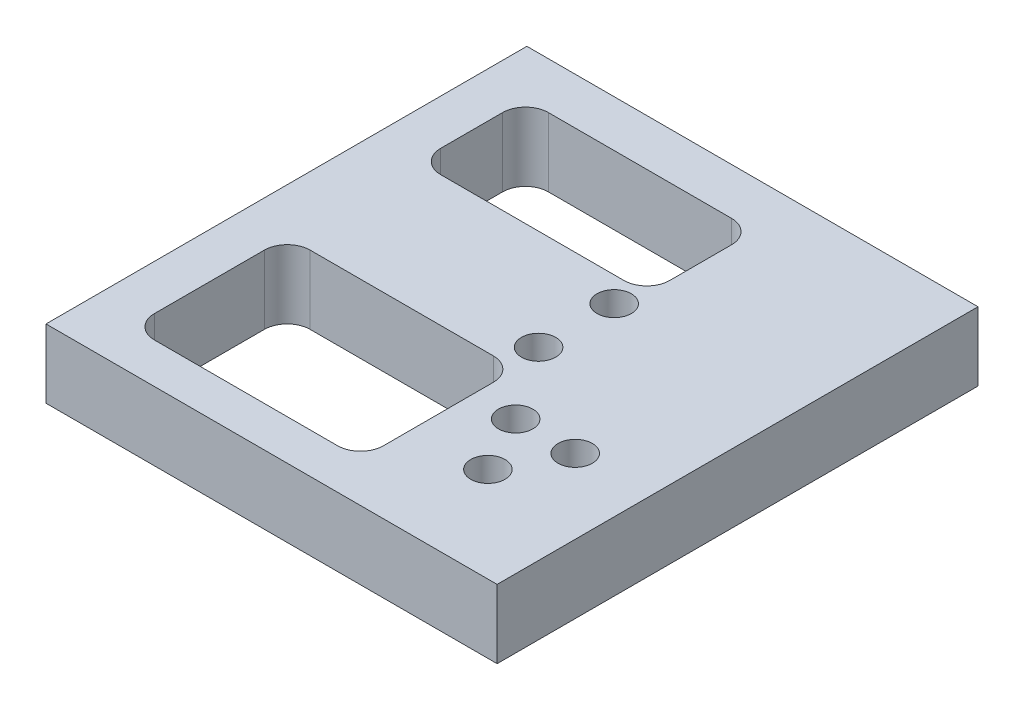
SolidWorks part; units mm, degrees
material "K110"
ref_plane "Front Plane" through (0, 0, 0) normal (0, 0, 1) x (1, 0, 0)
ref_plane "Top Plane" through (0, 0, 0) normal (0, 1, 0) x (1, 0, 0)
ref_plane "Right Plane" through (0, 0, 0) normal (1, 0, 0) x (0, 0, -1)
sketch "Sketch1" plane through (0, 0, 0) normal (0, 1, 0) x (1, 0, 0)
  line L1 (-98.5, -105) -> (98.5, -105)
  line L2 (-98.5, -105) -> (-98.5, 105)
  line L3 (-98.5, 105) -> (98.5, 105)
  line L4 (98.5, -105) -> (98.5, 105)
  line L5 (-98.5, -105) -> (98.5, 105) construction
  line L6 (-98.5, 105) -> (98.5, -105) construction
  point P0 (0, 0)
  dimension "D1" = 210
  dimension "D2" = 197
extrude "Boss-Extrude1" add sketch "Sketch1" against normal blind 30
sketch "Sketch2" plane through (0, 0, 0) normal (0, 1, 0) x (1, 0, 0)
  line L0 (-29.25, -63.53) -> (-29.25, -47.4) construction
  line L1 (-32.25, -44.4) -> (-36.25, -44.4) construction
  line L2 (-42.25, -38.4) -> (-42.25, -32.27) construction
  line L3 (-42.25, -32.27) -> (-61.37, -32.27) construction
  line L12 (-64.37, -35.27) -> (-64.37, -71.53) construction
  line L13 (-61.37, -74.53) -> (3.88, -74.53) construction
  line L14 (-17.25, -47.4) -> (-17.25, -63.53) construction
  line L15 (-10.25, -44.4) -> (-14.25, -44.4) construction
  line L16 (-4.25, -32.27) -> (-4.25, -38.4) construction
  line L17 (3.88, -32.27) -> (-4.25, -32.27) construction
  line L18 (6.88, -71.53) -> (6.88, -35.27) construction
  line L19 (-29.25, -63.53) -> (-29.25, -47.4)
  line L20 (-32.25, -44.4) -> (-36.25, -44.4)
  line L21 (-42.25, -38.4) -> (-42.25, -32.27)
  line L22 (-42.25, -32.27) -> (-61.37, -32.27)
  line L23 (-64.37, -35.27) -> (-64.37, -71.53)
  line L24 (-61.37, -74.53) -> (3.88, -74.53)
  line L25 (-17.25, -47.4) -> (-17.25, -63.53)
  line L26 (-10.25, -44.4) -> (-14.25, -44.4)
  line L27 (-4.25, -32.27) -> (-4.25, -38.4)
  line L28 (3.88, -32.27) -> (-4.25, -32.27)
  line L29 (6.88, -71.53) -> (6.88, -35.27)
  line L30 (-4.25, 47.73) -> (3.88, 47.73) construction
  line L31 (-4.25, 69.53) -> (-4.25, 47.73) construction
  line L32 (-42.25, 69.53) -> (-4.25, 69.53) construction
  line L33 (-42.25, 47.73) -> (-42.25, 69.53) construction
  line L34 (-61.37, 47.73) -> (-42.25, 47.73) construction
  line L35 (-64.37, 71.53) -> (-64.37, 50.73) construction
  line L36 (3.88, 74.53) -> (-61.37, 74.53) construction
  line L37 (6.88, 50.73) -> (6.88, 71.53) construction
  line L38 (-4.25, 47.73) -> (3.88, 47.73)
  line L39 (-4.25, 69.53) -> (-4.25, 47.73)
  line L40 (-42.25, 69.53) -> (-4.25, 69.53)
  line L41 (-42.25, 47.73) -> (-42.25, 69.53)
  line L42 (-61.37, 47.73) -> (-42.25, 47.73)
  line L43 (-64.37, 71.53) -> (-64.37, 50.73)
  line L44 (3.88, 74.53) -> (-61.37, 74.53)
  line L45 (6.88, 50.73) -> (6.88, 71.53)
  arc A0 (-29.25, -47.4) -> (-32.25, -44.4) centre (-32.25, -47.4) ccw construction
  arc A1 (-42.25, -38.4) -> (-36.25, -44.4) centre (-36.25, -38.4) ccw construction
  arc A2 (-61.37, -32.27) -> (-64.37, -35.27) centre (-61.37, -35.27) ccw construction
  arc A3 (-64.37, -71.53) -> (-61.37, -74.53) centre (-61.37, -71.53) ccw construction
  arc A4 (3.88, -74.53) -> (6.88, -71.53) centre (3.88, -71.53) ccw construction
  arc A5 (-29.25, -63.53) -> (-17.25, -63.53) centre (-23.25, -63.53) ccw construction
  arc A6 (-14.25, -44.4) -> (-17.25, -47.4) centre (-14.25, -47.4) ccw construction
  arc A7 (-10.25, -44.4) -> (-4.25, -38.4) centre (-10.25, -38.4) ccw construction
  arc A8 (6.88, -35.27) -> (3.88, -32.27) centre (3.88, -35.27) ccw construction
  arc A9 (-29.25, -47.4) -> (-32.25, -44.4) centre (-32.25, -47.4) ccw
  arc A10 (-42.25, -38.4) -> (-36.25, -44.4) centre (-36.25, -38.4) ccw
  arc A11 (-61.37, -32.27) -> (-64.37, -35.27) centre (-61.37, -35.27) ccw
  arc A12 (-64.37, -71.53) -> (-61.37, -74.53) centre (-61.37, -71.53) ccw
  arc A13 (3.88, -74.53) -> (6.88, -71.53) centre (3.88, -71.53) ccw
  arc A14 (-29.25, -63.53) -> (-17.25, -63.53) centre (-23.25, -63.53) ccw
  arc A15 (-14.25, -44.4) -> (-17.25, -47.4) centre (-14.25, -47.4) ccw
  arc A16 (-10.25, -44.4) -> (-4.25, -38.4) centre (-10.25, -38.4) ccw
  arc A17 (6.88, -35.27) -> (3.88, -32.27) centre (3.88, -35.27) ccw
  circle A18 centre (53, -63.53) radius 2.5 construction
  circle A19 centre (66, -38.4) radius 2.5 construction
  circle A20 centre (40, -38.4) radius 2.5 construction
  circle A21 centre (17.88, -6.27) radius 2.5 construction
  circle A22 centre (17.88, 26.73) radius 2.5 construction
  arc A23 (3.88, 47.73) -> (6.88, 50.73) centre (3.88, 50.73) ccw construction
  arc A24 (-64.37, 50.73) -> (-61.37, 47.73) centre (-61.37, 50.73) ccw construction
  arc A25 (-61.37, 74.53) -> (-64.37, 71.53) centre (-61.37, 71.53) ccw construction
  arc A26 (6.88, 71.53) -> (3.88, 74.53) centre (3.88, 71.53) ccw construction
  circle A27 centre (53, -63.53) radius 2.5
  circle A28 centre (66, -38.4) radius 2.5
  circle A29 centre (40, -38.4) radius 2.5
  circle A30 centre (17.88, -6.27) radius 2.5
  circle A31 centre (17.88, 26.73) radius 2.5
  arc A32 (3.88, 47.73) -> (6.88, 50.73) centre (3.88, 50.73) ccw
  arc A33 (-64.37, 50.73) -> (-61.37, 47.73) centre (-61.37, 50.73) ccw
  arc A34 (-61.37, 74.53) -> (-64.37, 71.53) centre (-61.37, 71.53) ccw
  arc A35 (6.88, 71.53) -> (3.88, 74.53) centre (3.88, 71.53) ccw
sketch "Sketch3" plane through (0, 0, 0) normal (0, 1, 0) x (1, 0, 0)
  line L1 (-68.745, 84.63) -> (11.255, 84.63)
  line L2 (-78.745, 74.63) -> (-78.745, 47.63)
  line L3 (-68.745, 37.63) -> (11.255, 37.63)
  line L4 (21.255, 74.63) -> (21.255, 47.63)
  line L8 (-64.37, -53.4) -> (6.88, -53.4) construction
  line L9 (-68.745, -19.4) -> (11.255, -19.4)
  line L10 (-78.745, -29.4) -> (-78.745, -77.4)
  line L11 (-68.745, -87.4) -> (11.255, -87.4)
  line L12 (21.255, -29.4) -> (21.255, -77.4)
  line L13 (-64.37, -35.27) -> (-64.37, -71.53) construction
  line L14 (6.88, -71.53) -> (6.88, -35.27) construction
  line L15 (-28.745, -74.53) -> (-28.745, -19.4) construction
  line L16 (-61.37, -74.53) -> (3.88, -74.53) construction
  line L17 (-28.745, 84.63) -> (-28.745, 47.73) construction
  line L18 (-64.37, 61.13) -> (6.88, 61.13) construction
  line L19 (-64.37, 71.53) -> (-64.37, 50.73) construction
  line L20 (6.88, 50.73) -> (6.88, 71.53) construction
  arc A0 (-78.745, 47.63) -> (-68.745, 37.63) centre (-68.745, 47.63) ccw
  arc A1 (11.255, 37.63) -> (21.255, 47.63) centre (11.255, 47.63) ccw
  arc A2 (21.255, 74.63) -> (11.255, 84.63) centre (11.255, 74.63) ccw
  arc A3 (-68.745, 84.63) -> (-78.745, 74.63) centre (-68.745, 74.63) ccw
  circle A4 centre (17.88, 26.73) radius 7.5
  circle A5 centre (17.88, -6.27) radius 7.5
  circle A6 centre (53, -63.53) radius 7.5
  circle A7 centre (66, -38.4) radius 7.5
  circle A8 centre (40, -38.4) radius 7.5
  arc A9 (-78.745, -77.4) -> (-68.745, -87.4) centre (-68.745, -77.4) ccw
  arc A10 (11.255, -87.4) -> (21.255, -77.4) centre (11.255, -77.4) ccw
  arc A11 (21.255, -29.4) -> (11.255, -19.4) centre (11.255, -29.4) ccw
  arc A12 (-68.745, -19.4) -> (-78.745, -29.4) centre (-68.745, -29.4) ccw
  dimension "D5" = 10
  dimension "D6" = 15
  dimension "D11" = 10
  dimension "D2" = 100
  dimension "D3" = 47
  dimension "D7" = 68
  dimension "D8" = 100
extrude "Cut-Extrude2" cut sketch "Sketch3" against normal up to next
sketch "Sketch4" plane through (0, -30, 0) normal (0, -1, 0) x (1, 0, 0)
  circle A0 centre (17.88, -26.73) radius 9
  circle A1 centre (17.88, 6.27) radius 9
  circle A2 centre (40, 38.4) radius 9
  circle A3 centre (66, 38.4) radius 9
  circle A4 centre (53, 63.53) radius 9
  dimension "D1" = 18
extrude "Cut-Extrude3" cut sketch "Sketch4" against normal blind 5
